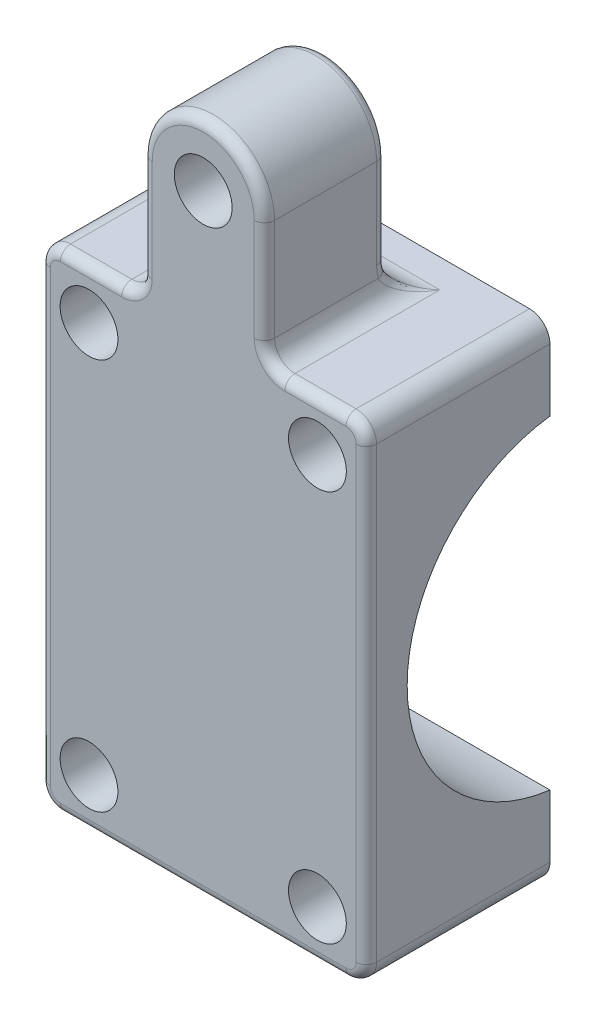
SolidWorks part; units mm, degrees
ref_plane "Front Plane" through (0, 0, 0) normal (0, 0, 1) x (1, 0, 0)
ref_plane "Top Plane" through (0, 0, 0) normal (0, 1, 0) x (1, 0, 0)
ref_plane "Right Plane" through (0, 0, 0) normal (1, 0, 0) x (0, 0, -1)
sketch "Sketch1" plane through (0, 0, 0) normal (0, 0, 1) x (1, 0, 0)
  line L0 (-4.7625, 28.575) -> (-4.7625, 20.6375)
  line L1 (11.1125, -19.05) -> (-11.1125, -19.05)
  line L2 (12.7, -17.4625) -> (12.7, 17.4625)
  line L3 (11.1125, 19.05) -> (6.35, 19.05)
  line L4 (-12.7, -17.4625) -> (-12.7, 17.4625)
  line L5 (12.7, -19.05) -> (-12.7, 19.05) construction
  line L6 (12.7, 19.05) -> (-12.7, -19.05) construction
  line L7 (4.7625, 28.575) -> (4.7625, 20.6375)
  line L8 (-6.35, 19.05) -> (-11.1125, 19.05)
  line L9 (-8.89, 15.24) -> (8.89, -15.24) construction
  circle A0 centre (0, 28.575) radius 2.25
  arc A1 (4.7625, 28.575) -> (-4.7625, 28.575) centre (0, 28.575) ccw
  arc A2 (4.7625, 20.6375) -> (6.35, 19.05) centre (6.35, 20.6375) ccw
  arc A3 (-4.7625, 20.6375) -> (-6.35, 19.05) centre (-6.35, 20.6375) cw
  circle A4 centre (0, 28.575) radius 7 construction
  circle A5 centre (-8.89, 15.24) radius 2.25
  arc A6 (11.1125, -19.05) -> (12.7, -17.4625) centre (11.1125, -17.4625) ccw
  arc A7 (-11.1125, -19.05) -> (-12.7, -17.4625) centre (-11.1125, -17.4625) cw
  arc A8 (12.7, 17.4625) -> (11.1125, 19.05) centre (11.1125, 17.4625) ccw
  arc A9 (-11.1125, 19.05) -> (-12.7, 17.4625) centre (-11.1125, 17.4625) ccw
  circle A10 centre (8.89, 15.24) radius 2.25
  circle A11 centre (8.89, -15.24) radius 2.25
  circle A12 centre (-8.89, -15.24) radius 2.25
  point P0 (0, 0)
  point P16 (-4.7625, 19.05)
  point P33 (0, 0)
  point P34 (-9.525, -15.875)
  point P40 (0, 0)
  dimension "D3" = 4.5
  dimension "D5" = 1.5875
  dimension "D6" = 14
  dimension "D7" = 4.7625
  dimension "D8" = 4.5
  dimension "D11" = 1.5875
  dimension "D1" = 38.1
  dimension "D2" = 25.4
  dimension "D4" = 9.525
  dimension "D9" = 3.81
  dimension "D10" = 3.81
  dimension "D12" = 2
  dimension "D13" = 2
extrude "Boss-Extrude1" add sketch "Sketch1" along normal blind 31.75
sketch "Sketch2" plane through (12.7, 0, 0) normal (1, 0, 0) x (0, 0, -1)
  line L0 (0, 19.05) -> (-31.75, -19.05) construction
  line L1 (-31.75, -19.05) -> (0, -19.05) construction
  line L2 (-31.75, 19.05) -> (0, 19.05) construction
  line L3 (-31.75, -19.05) -> (0, -19.05)
  line L4 (-31.75, 19.05) -> (0, 19.05)
  circle A0 centre (-15.875, 0) radius 12.7
  point P8 (0, 0)
  dimension "D1" = 25.4
extrude "Cut-Extrude1" cut sketch "Sketch2" against normal blind 28.575 contours L0 A0 | A0 L0 region at (12.7, -3.4506, 11.7343) region at (12.7, 3.4506, 20.0157)
sketch "Sketch3" plane through (0, 0, 0) normal (0, 0, -1) x (-1, 0, 0)
  line L0 (-6.35, 19.05) -> (6.35, 19.05)
  line L7 (-4.7625, 28.575) -> (-4.7625, 20.6375)
  line L8 (-6.35, 19.05) -> (-11.1125, 19.05)
  line L9 (-12.7, 17.4625) -> (-12.7, -17.4625)
  line L10 (-11.1125, -19.05) -> (11.1125, -19.05)
  line L11 (12.7, -17.4625) -> (12.7, 17.4625)
  line L12 (11.1125, 19.05) -> (6.35, 19.05)
  line L13 (4.7625, 20.6375) -> (4.7625, 28.575)
  line L14 (-4.7625, 28.575) -> (-4.7625, 20.6375)
  line L15 (-6.35, 19.05) -> (-11.1125, 19.05)
  line L16 (-12.7, 17.4625) -> (-12.7, -17.4625)
  line L17 (-11.1125, -19.05) -> (11.1125, -19.05)
  line L18 (12.7, -17.4625) -> (12.7, 17.4625)
  line L19 (11.1125, 19.05) -> (6.35, 19.05)
  line L20 (4.7625, 20.6375) -> (4.7625, 28.575)
  arc A7 (4.7625, 28.575) -> (-4.7625, 28.575) centre (0, 28.575) ccw
  arc A8 (-6.35, 19.05) -> (-4.7625, 20.6375) centre (-6.35, 20.6375) ccw
  arc A9 (-11.1125, 19.05) -> (-12.7, 17.4625) centre (-11.1125, 17.4625) ccw
  arc A10 (-12.7, -17.4625) -> (-11.1125, -19.05) centre (-11.1125, -17.4625) ccw
  arc A11 (11.1125, -19.05) -> (12.7, -17.4625) centre (11.1125, -17.4625) ccw
  arc A12 (12.7, 17.4625) -> (11.1125, 19.05) centre (11.1125, 17.4625) ccw
  arc A13 (4.7625, 20.6375) -> (6.35, 19.05) centre (6.35, 20.6375) ccw
  arc A14 (4.7625, 28.575) -> (-4.7625, 28.575) centre (0, 28.575) ccw
  arc A15 (-6.35, 19.05) -> (-4.7625, 20.6375) centre (-6.35, 20.6375) ccw
  arc A16 (-11.1125, 19.05) -> (-12.7, 17.4625) centre (-11.1125, 17.4625) ccw
  arc A17 (-12.7, -17.4625) -> (-11.1125, -19.05) centre (-11.1125, -17.4625) ccw
  arc A18 (11.1125, -19.05) -> (12.7, -17.4625) centre (11.1125, -17.4625) ccw
  arc A19 (12.7, 17.4625) -> (11.1125, 19.05) centre (11.1125, 17.4625) ccw
  arc A20 (4.7625, 20.6375) -> (6.35, 19.05) centre (6.35, 20.6375) ccw
  arc M15 (4.7625, 28.575) -> (-4.7625, 28.575) centre (0, 28.575) ccw
  line M16 (-4.7625, 28.575) -> (-4.7625, 20.6375)
  arc M17 (-4.7625, 20.6375) -> (-6.35, 19.05) centre (-6.35, 20.6375) cw
  arc M27 (6.35, 19.05) -> (4.7625, 20.6375) centre (6.35, 20.6375) cw
  line M28 (4.7625, 20.6375) -> (4.7625, 28.575)
  circle M29 centre (0, 28.575) radius 2.25
  dimension "D1" = 0
extrude "Cut-Extrude2" cut sketch "Sketch3" against normal offset from surface (12.7 mm away) 9.525 from offset 9.525 contours L0 M17 M27 M28 M15 M16 M29 region at (0, 25.2577, 0) up to face at (11.14, -15.24, 31.75) offset against normal yes
fillet "Fillet1" radius 2.54 2 edges at (0, 19.05, 22.225) (0, 19.05, 9.525)
fillet "Fillet2" radius 0.7937 42 edges at (-5.1262, 19.6263, 10.4539) (-4.7625, 21.1048, 9.5718) (-4.7625, 25.0825, 9.525) (0, 33.3375, 9.525) (5.1262, 19.6263, 10.4539) (4.7625, 21.1048, 9.5718) (-5.1262, 19.6263, 21.2961) (-4.7625, 21.1048, 22.1782) (-4.7625, 25.0825, 22.225) (0, 33.3375, 22.225) (5.1262, 19.6263, 21.2961) (4.7625, 21.1048, 22.1782) (12.235, -18.585, 31.75) (0, -19.05, 31.75) (-12.235, -18.585, 31.75) (-12.7, 0, 31.75) (-12.235, 18.585, 31.75) (-8.7312, 19.05, 31.75) (-5.2275, 19.515, 31.75) (-4.7625, 24.6062, 31.75) (0, 33.3375, 31.75) (4.7625, 24.6062, 31.75) (5.2275, 19.515, 31.75) (8.7312, 19.05, 31.75) (12.235, 18.585, 31.75) (12.235, -18.585, 0) (0, -19.05, 0) (-12.235, -18.585, 0) (-12.7, 0, 0) (-12.235, 18.585, 0) (-8.7312, 19.05, 0) (-5.2275, 19.515, 0) (-4.7625, 24.6062, 0) (0, 33.3375, 0) (4.7625, 24.6062, 0) (5.2275, 19.515, 0) (8.7312, 19.05, 0) (12.235, 18.585, 0) (4.7625, 25.0825, 9.525) (4.7625, 25.0825, 22.225) (12.7, 0, 31.75) (12.7, 0, 0)
sketch "Sketch4" plane through (0, 0, 0) normal (0, 0, -1) x (-1, 0, 0)
  line L1 (27.8449, -35.1119) -> (-27.8449, -35.1119)
  line L2 (27.8449, -35.1119) -> (27.8449, 35.1119)
  line L3 (27.8449, 35.1119) -> (-27.8449, 35.1119)
  line L4 (-27.8449, -35.1119) -> (-27.8449, 35.1119)
  line L5 (27.8449, -35.1119) -> (-27.8449, 35.1119) construction
  line L6 (27.8449, 35.1119) -> (-27.8449, -35.1119) construction
  point P0 (0, 0)
extrude "Cut-Extrude3" cut sketch "Sketch4" against normal blind 17.4625
